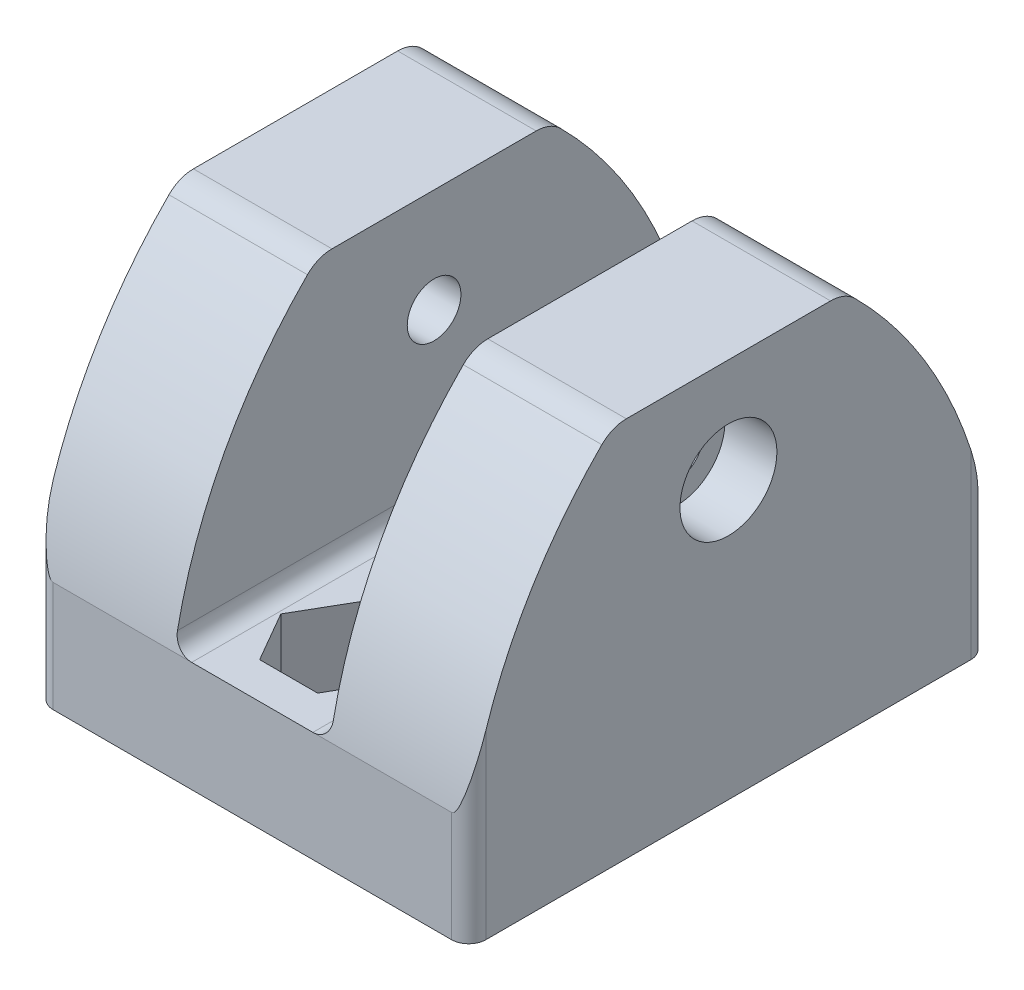
SolidWorks part; units mm, degrees
ref_plane "Alzado" through (0, 0, 0) normal (0, 0, 1) x (1, 0, 0)
ref_plane "Planta" through (0, 0, 0) normal (0, 1, 0) x (1, 0, 0)
ref_plane "Vista lateral" through (0, 0, 0) normal (1, 0, 0) x (0, 0, -1)
sketch "Croquis1" plane through (0, 0, 0) normal (0, 1, 0) x (1, 0, 0)
  line L0 (12.5, 30) -> (12.5, 0) construction
  line L1 (0, 0) -> (25, 0)
  line L2 (0, 0) -> (0, 30)
  line L3 (0, 30) -> (25, 30)
  line L4 (25, 0) -> (25, 30)
  circle A0 centre (12.5, 25) radius 1.55
  circle A1 centre (12.5, 5) radius 1.55
  dimension "D3" = 20
  dimension "D4" = 3.1
  dimension "D1" = 25
  dimension "D2" = 30
  dimension "D5" = 5
extrude "Saliente-Extruir1" add sketch "Croquis1" along normal blind 22
sketch "Croquis2" plane through (0, 0, -30) normal (0, 0, -1) x (-1, 0, 0)
  line L0 (-25, 22) -> (0, 22) construction
  line L1 (-8, 22) -> (-17, 22)
  line L2 (-8, 22) -> (-8, 6.3673)
  line L3 (-8, 6.3673) -> (-17, 6.3673)
  line L4 (-17, 22) -> (-17, 6.3673)
  line L5 (0, 22) -> (0, 0) construction
  dimension "D1" = 9
  dimension "D2" = 8
extrude "Cortar-Extruir1" cut sketch "Croquis2" against normal up to surface (30 mm away) up to face at (12.5, 11, 0)
sketch "Croquis3" plane through (0, 0, 0) normal (-1, 0, 0) x (0, 0, 1)
  line L0 (-15, 0) -> (-15, 22) construction
  line L1 (-30, 0) -> (0, 0) construction
  line L2 (-30, 22) -> (0, 22) construction
  circle A0 centre (-15, 16) radius 1.55
  dimension "D1" = 3.1
  dimension "D2" = 6
extrude "Cortar-Extruir2" cut sketch "Croquis3" against normal up to surface (25 mm away) up to face at (25, 11, -15)
sketch "Croquis4" plane through (0, 0, 0) normal (-1, 0, 0) x (0, 0, 1)
  line L1 (-14.9679, 19.3485) -> (-17.8838, 17.702)
  line L2 (-17.8838, 17.702) -> (-17.9159, 14.3536)
  line L3 (-17.9159, 14.3536) -> (-15.0321, 12.6515)
  line L4 (-15.0321, 12.6515) -> (-12.1162, 14.298)
  line L5 (-12.1162, 14.298) -> (-12.0841, 17.6464)
  line L6 (-12.0841, 17.6464) -> (-14.9679, 19.3485)
  circle A0 centre (-15, 16) radius 2.9 construction
  dimension "D1" = 5.8
extrude "Cortar-Extruir3" cut sketch "Croquis4" against normal blind 2.5
sketch "Croquis5" plane through (25, 0, 0) normal (1, 0, 0) x (0, 0, -1)
  circle A0 centre (15, 16) radius 2.8
  dimension "D1" = 5.6
extrude "Cortar-Extruir4" cut sketch "Croquis5" against normal blind 3
sketch "Croquis6" plane through (0, 6.3673, 0) normal (0, 1, 0) x (1, 0, 0)
  line L1 (15.8486, 25) -> (14.1743, 27.9)
  line L2 (14.1743, 27.9) -> (10.8257, 27.9)
  line L3 (10.8257, 27.9) -> (9.1514, 25)
  line L4 (9.1514, 25) -> (10.8257, 22.1)
  line L5 (10.8257, 22.1) -> (14.1743, 22.1)
  line L6 (14.1743, 22.1) -> (15.8486, 25)
  line L7 (15.8486, 5) -> (14.1743, 7.9)
  line L8 (14.1743, 7.9) -> (10.8257, 7.9)
  line L9 (10.8257, 7.9) -> (9.1514, 5)
  line L10 (9.1514, 5) -> (10.8257, 2.1)
  line L11 (10.8257, 2.1) -> (14.1743, 2.1)
  line L12 (14.1743, 2.1) -> (15.8486, 5)
  circle A0 centre (12.5, 25) radius 2.9 construction
  circle A1 centre (12.5, 5) radius 2.9 construction
  dimension "D1" = 5.8
  dimension "D2" = 5.8
extrude "Cortar-Extruir5" cut sketch "Croquis6" against normal blind 4.5
sketch "Croquis7" plane through (0, 0, 0) normal (-1, 0, 0) x (0, 0, 1)
  line L0 (-15, 0) -> (-15, 22) construction
  line L1 (-30, 0) -> (0, 0) construction
  line L2 (-30, 22) -> (0, 22) construction
  line L3 (-30, 22) -> (-30, 6.37)
  line L4 (-30, 22) -> (-30, 0) construction
  line L5 (-30, 22) -> (-21.7082, 22)
  line L6 (0, 22) -> (-8.2918, 22)
  line L7 (0, 22) -> (0, 6.37)
  circle A0 centre (-15, 16) radius 9
  arc A1 (-30, 6.37) -> (-21.7082, 22) centre (-2.8457, 1.9789) cw
  arc A2 (0, 6.37) -> (-8.2918, 22) centre (-27.1543, 1.9789) ccw
  line M8 (0, 0) -> (0, 22)
  line M9 (0, 22) -> (-30, 22)
  line M10 (-30, 22) -> (-30, 0)
  dimension "D1" = 18
  dimension "D2" = 6.37
extrude "Cortar-Extruir6" cut sketch "Croquis7" against normal up to surface (25 mm away) contours A1 M10 M9 | A2 M8 M9 region at (0, 17.6409, -27.5517) region at (0, 17.6409, -2.4483) up to face at (25, 16, -17.8)
fillet "Redondeo1" radius 2 4 edges at (21, 22, -21.7082) (21, 22, -8.2918) (4, 22, -8.2918) (4, 22, -21.7082)
fillet "Redondeo2" radius 1 2 edges at (17, 6.3673, -15) (8, 6.3673, -15)
fillet "Redondeo3" radius 1 4 edges at (25, 3.185, 0) (0, 3.185, 0) (0, 3.185, -30) (25, 3.185, -30)
